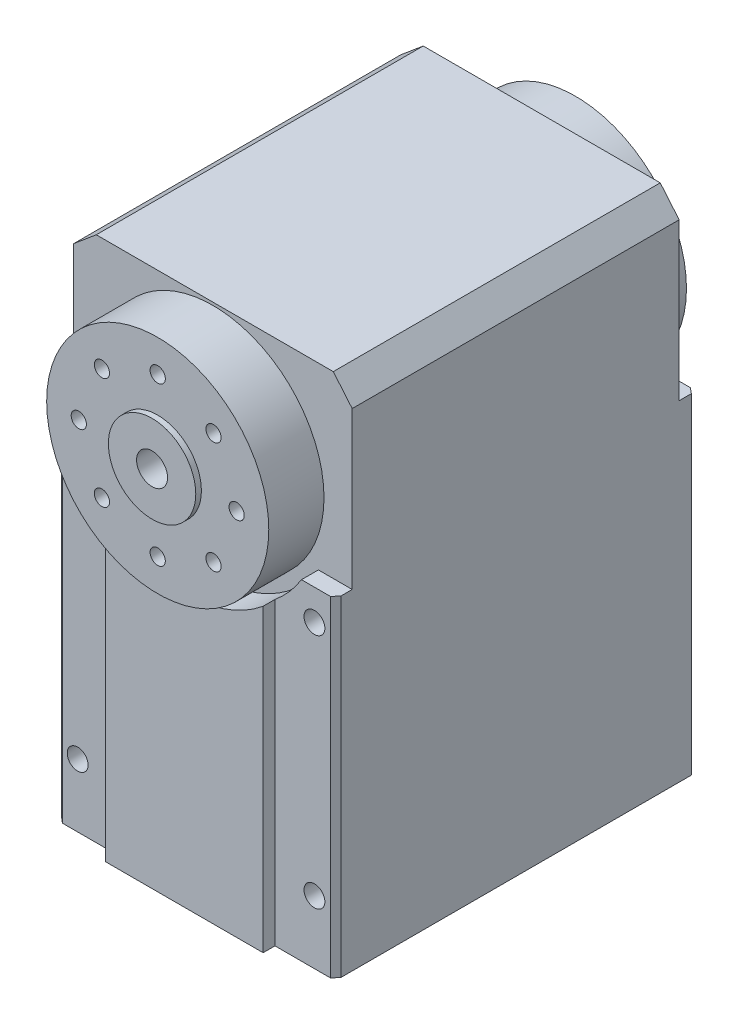
SolidWorks part; units mm, degrees
note: The reader was unsure of these and kept them because the rebuilt part matched: shared geometry of "Sketch1<3>", "Sketch1<4>", "Sketch1<5>", "Sketch3<3>", "Sketch4<3>", "Sketch5<2>".
ref_plane "Front Plane" through (0, 0, 0) normal (0, 0, 1) x (1, 0, 0)
ref_plane "Top Plane" through (0, 0, 0) normal (0, 1, 0) x (1, 0, 0)
ref_plane "Right Plane" through (0, 0, 0) normal (1, 0, 0) x (0, 0, -1)
sketch "Sketch1" plane through (0, 0, 0) normal (0, 0, 1) x (1, 0, 0)
  line L0 (-12.35, -5.7946) -> (-9.35, -5.7946)
  line L1 (-12.35, -35.1) -> (12.35, -35.1)
  line L2 (-12.35, -35.1) -> (-12.35, 10.1)
  line L3 (-12.35, 10.1) -> (12.35, 10.1)
  line L4 (12.35, -35.1) -> (12.35, 10.1)
  line L5 (-12.35, -35.1) -> (12.35, 10.1) construction
  line L6 (-12.35, 10.1) -> (12.35, -35.1) construction
  line L7 (0, -55) -> (0, 55) construction
  line L8 (12.35, -5.7946) -> (9.35, -5.7946)
  circle A0 centre (0, 0) radius 9.85
  arc A1 (-9.35, -5.7946) -> (9.35, -5.7946) centre (0, 0) ccw
  circle A2 centre (0, 0) radius 7 construction
  circle A3 centre (0, 7) radius 0.675
  circle A4 centre (4.9497, 4.9497) radius 0.675
  circle A5 centre (7, 0) radius 0.675
  circle A6 centre (4.9497, -4.9497) radius 0.675
  circle A7 centre (0, -7) radius 0.675
  circle A8 centre (-4.9497, -4.9497) radius 0.675
  circle A9 centre (-7, 0) radius 0.675
  circle A10 centre (-4.9497, 4.9497) radius 0.675
  point P0 (0, -12.5)
  point P34 (0, 0)
  dimension "D4" = 19.7
  dimension "D5" = 11
  dimension "D7" = 14
  dimension "D8" = 1.35
  dimension "D1" = 24.7
  dimension "D2" = 45.2
  dimension "D3" = 10.1
  dimension "D6" = 3
  dimension "D9" = 8
extrude "Boss-Extrude1" add sketch "Sketch1" along normal mid plane 29 contours A3 | A4 | A5 | A6 | A7 | A8 | A9 | A10 | A0 A10 A9 A8 A7 A6 A5 A4 A3 | L0 A1 L8 L4 L3 L2 A0 | A1 L0 L2 L1 L4 L8
extrude "Boss-Extrude2" add sketch "Sketch1<3>" along normal mid plane 32 contours A1 L0 L2 L1 L4 L8
sketch "Sketch1<3>" plane through (0, 0, 0) normal (0, 0, 1) x (1, 0, 0) same geometry as "Sketch1"
extrude "Boss-Extrude3" add sketch "Sketch1<4>" along normal blind 4.9 from surface at 14.5 contours A0
sketch "Sketch1<4>" plane through (0, 0, 0) normal (0, 0, 1) x (1, 0, 0) same geometry as "Sketch1"
extrude "Boss-Extrude4" add sketch "Sketch1<5>" against normal blind 3.15 from surface at -14.5 contours A0
sketch "Sketch1<5>" plane through (0, 0, 0) normal (0, 0, 1) x (1, 0, 0) same geometry as "Sketch1"
sketch "Sketch2" plane through (0, 0, 16) normal (0, 0, 1) x (1, 0, 0)
  line L0 (-7, -8.4853) -> (-7, -35.1)
  line L1 (-12.35, -35.1) -> (12.35, -35.1) construction
  line L2 (0, -55) -> (0, 55) construction
  line L3 (7, -8.4853) -> (7, -35.1)
  line L4 (-7, -35.1) -> (7, -35.1)
  arc A0 (-9.35, -5.7946) -> (9.35, -5.7946) centre (0, 0) ccw construction
  arc A1 (-7, -8.4853) -> (7, -8.4853) centre (0, 0) ccw
  dimension "D1" = 14
extrude "Boss-Extrude5" add sketch "Sketch2" along normal blind 1.05
sketch "Sketch3" plane through (0, 0, -16) normal (0, 0, -1) x (-1, 0, 0)
  line L1 (-9.25, -30.5) -> (9.25, -30.5)
  line L2 (-9.25, -30.5) -> (-9.25, -17)
  line L3 (-9.25, -17) -> (9.25, -17)
  line L4 (9.25, -30.5) -> (9.25, -17)
  line L5 (-9.25, -30.5) -> (9.25, -17) construction
  line L6 (-9.25, -17) -> (9.25, -30.5) construction
  line L7 (-10, -12) -> (10, -12)
  line L8 (-10, -12) -> (-10, -17)
  line L9 (-10, -17) -> (10, -17)
  line L10 (10, -12) -> (10, -17)
  line L11 (-10, -12) -> (10, -17) construction
  line L12 (-10, -17) -> (10, -12) construction
  point P0 (0, -23.75)
  point P7 (0, -14.5)
  dimension "D1" = 18.5
  dimension "D2" = 18.5
  dimension "D3" = 5
  dimension "D4" = 20
  dimension "D5" = 14.5
  dimension "D6" = 12
extrude "Boss-Extrude6" add sketch "Sketch3" along normal blind 1.85 contours L1 L4 L3 L2
chamfer "Chamfer1" distance 2.1 angle 40 1 edges at (0, -17, -17.85)
extrude "Boss-Extrude7" add sketch "Sketch3<3>" along normal blind 1.5 contours L10 L7 L8 L9 L3
sketch "Sketch3<3>" plane through (0, 0, -16) normal (0, 0, -1) x (-1, 0, 0) same geometry as "Sketch3"
sketch "Sketch4" plane through (0, 0, 0) normal (0, 0, 1) x (1, 0, 0)
  line L0 (0, -55) -> (0, 55) construction
  line L1 (-12.35, -35.1) -> (-7, -35.1) construction
  line L2 (-12.35, 10.1) -> (12.35, 10.1) construction
  line L3 (-12.35, 10.1) -> (12.35, 10.1) construction
  line L4 (7, -35.1) -> (12.35, -35.1) construction
  circle A0 centre (-10.5, -8.5) radius 0.925
  circle A1 centre (-10.5, -33) radius 0.925
  circle A2 centre (10.5, -33) radius 0.925
  circle A3 centre (10.5, -8.5) radius 0.925
  circle A4 centre (-10.5, -29.5) radius 0.925
  circle A5 centre (10.5, -29.5) radius 0.925
  dimension "D1" = 1.85
  dimension "D2" = 24.5
  dimension "D3" = 21
  dimension "D4" = 8.5
  dimension "D5" = 2.1
  dimension "D6" = 10.1
  dimension "D7" = 21
  dimension "D8" = 5.6
extrude "Cut-Extrude1" cut sketch "Sketch4" against normal blind 5 from surface at 16 contours A0 | A3 | A4 | A5 starting at face at (-9.632, -18.0741, 16)
extrude "Cut-Extrude2" cut sketch "Sketch4<3>" along normal blind 5 from surface at -16 contours A3 | A0 | A1 | A2 starting at face at (0, -16.4306, -16)
sketch "Sketch4<3>" plane through (0, 0, 0) normal (0, 0, 1) x (1, 0, 0) same geometry as "Sketch4"
chamfer "Chamfer2" distance 2 angle 40 2 edges at (-12.35, 10.1, 0) (12.35, 10.1, 0)
chamfer "Chamfer3" distance 0.5 angle 40 4 edges at (-12.35, -20.4473, -16) (12.35, -20.4473, -16) (12.35, -20.4473, 16) (-12.35, -20.4473, 16)
sketch "Sketch5" plane through (0, 0, 0) normal (0, 0, 1) x (1, 0, 0)
  circle A0 centre (0, 0) radius 3.875
  dimension "D1" = 7.75
extrude "Boss-Extrude8" add sketch "Sketch5" along normal blind 0.5 from surface at 19.4 starting at face at (-6.325, 0, 19.4)
extrude "Boss-Extrude9" add sketch "Sketch5<2>" against normal blind 0.55 from surface at -17.65 starting at face at (-4.2747, 4.9497, -17.65)
sketch "Sketch5<2>" plane through (0, 0, 0) normal (0, 0, 1) x (1, 0, 0) same geometry as "Sketch5"
sketch "Sketch6" plane through (0, 0, 0) normal (0, 0, 1) x (1, 0, 0)
  circle A0 centre (0, 0) radius 1.375
  dimension "D1" = 2.75
extrude "Cut-Extrude3" cut sketch "Sketch6" against normal through all both and the other way through all
